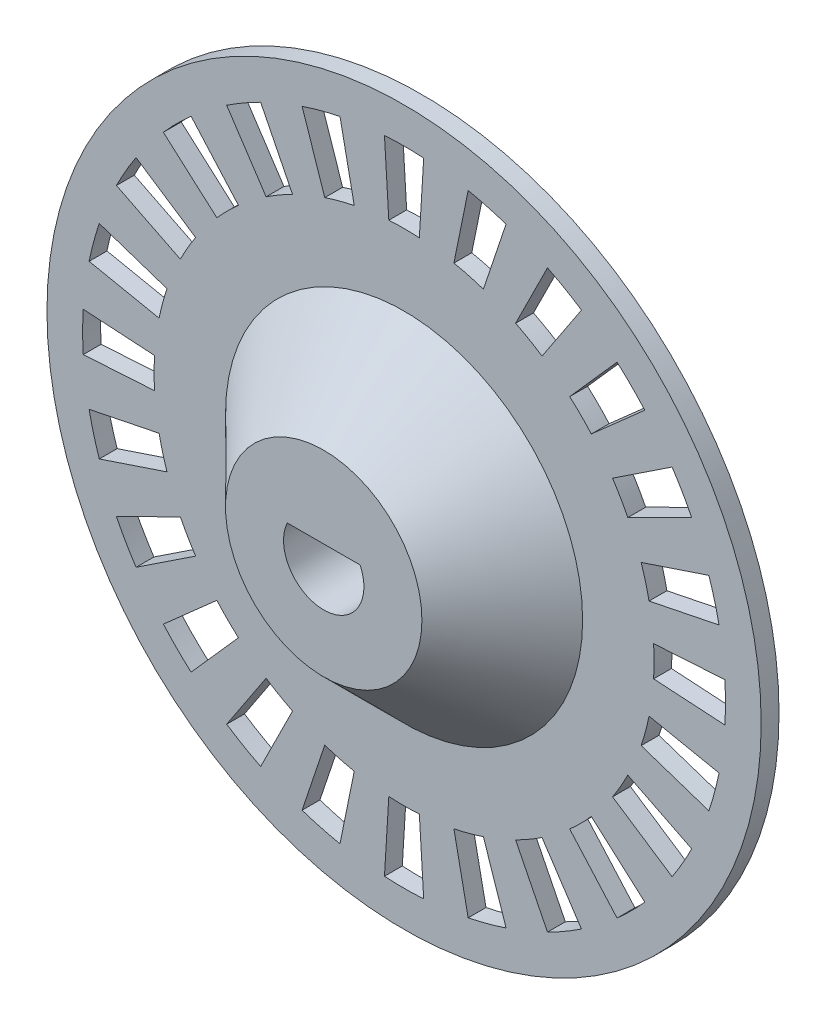
SolidWorks part; units mm, degrees
ref_plane "Alzado" through (0, 0, 0) normal (0, 0, 1) x (1, 0, 0)
ref_plane "Planta" through (0, 0, 0) normal (0, 1, 0) x (1, 0, 0)
ref_plane "Vista lateral" through (0, 0, 0) normal (1, 0, 0) x (0, 0, -1)
sketch "Croquis2" plane through (0, 0, 0) normal (0, 0, 1) x (1, 0, 0)
  line L0 (-2.0396, 0.95) -> (2.0396, 0.95)
  line L1 (-2.5594, -2.25) -> (2.5594, -2.25) construction
  line L2 (0, 18) -> (0, -18) construction
  line L3 (18, 0) -> (-18, 0) construction
  line L4 (-1.0989, 17.9664) -> (-0.8547, 13.9739)
  line L5 (0.8547, 13.9739) -> (1.0989, 17.9664)
  line L6 (3.5886, 17.6386) -> (2.7912, 13.7189)
  line L7 (4.4423, 13.2765) -> (5.7115, 17.0698)
  line L8 (8.0316, 16.1088) -> (6.2468, 12.5291)
  line L9 (7.7271, 11.6744) -> (9.9349, 15.0099)
  line L10 (11.9272, 13.4812) -> (9.2767, 10.4854)
  line L11 (10.4854, 9.2767) -> (13.4812, 11.9272)
  line L12 (15.0099, 9.9349) -> (11.6744, 7.7271)
  line L13 (12.5291, 6.2468) -> (16.1088, 8.0316)
  line L14 (17.0698, 5.7115) -> (13.2765, 4.4423)
  line L15 (13.7189, 2.7912) -> (17.6386, 3.5886)
  line L16 (17.9664, 1.0989) -> (13.9739, 0.8547)
  line L17 (13.9739, -0.8547) -> (17.9664, -1.0989)
  line L18 (17.6386, -3.5886) -> (13.7189, -2.7912)
  line L19 (13.2765, -4.4423) -> (17.0698, -5.7115)
  line L20 (16.1088, -8.0316) -> (12.5291, -6.2468)
  line L21 (11.6744, -7.7271) -> (15.0099, -9.9349)
  line L22 (13.4812, -11.9272) -> (10.4854, -9.2767)
  line L23 (9.2767, -10.4854) -> (11.9272, -13.4812)
  line L24 (9.9349, -15.0099) -> (7.7271, -11.6744)
  line L25 (6.2468, -12.5291) -> (8.0316, -16.1088)
  line L26 (5.7115, -17.0698) -> (4.4423, -13.2765)
  line L27 (2.7912, -13.7189) -> (3.5886, -17.6386)
  line L28 (1.0989, -17.9664) -> (0.8547, -13.9739)
  line L29 (-0.8547, -13.9739) -> (-1.0989, -17.9664)
  line L30 (-3.5886, -17.6386) -> (-2.7912, -13.7189)
  line L31 (-4.4423, -13.2765) -> (-5.7115, -17.0698)
  line L32 (-8.0316, -16.1088) -> (-6.2468, -12.5291)
  line L33 (-7.7271, -11.6744) -> (-9.9349, -15.0099)
  line L34 (-11.9272, -13.4812) -> (-9.2767, -10.4854)
  line L35 (-10.4854, -9.2767) -> (-13.4812, -11.9272)
  line L36 (-15.0099, -9.9349) -> (-11.6744, -7.7271)
  line L37 (-12.5291, -6.2468) -> (-16.1088, -8.0316)
  line L38 (-17.0698, -5.7115) -> (-13.2765, -4.4423)
  line L39 (-13.7189, -2.7912) -> (-17.6386, -3.5886)
  line L40 (-17.9664, -1.0989) -> (-13.9739, -0.8547)
  line L41 (-13.9739, 0.8547) -> (-17.9664, 1.0989)
  line L42 (-17.6386, 3.5886) -> (-13.7189, 2.7912)
  line L43 (-13.2765, 4.4423) -> (-17.0698, 5.7115)
  line L44 (-16.1088, 8.0316) -> (-12.5291, 6.2468)
  line L45 (-11.6744, 7.7271) -> (-15.0099, 9.9349)
  line L46 (-13.4812, 11.9272) -> (-10.4854, 9.2767)
  line L47 (-9.2767, 10.4854) -> (-11.9272, 13.4812)
  line L48 (-9.9349, 15.0099) -> (-7.7271, 11.6744)
  line L49 (-6.2468, 12.5291) -> (-8.0316, 16.1088)
  line L50 (-5.7115, 17.0698) -> (-4.4423, 13.2765)
  line L51 (-2.7912, 13.7189) -> (-3.5886, 17.6386)
  circle A0 centre (0, 0) radius 14
  circle A1 centre (0, 0) radius 2.25
  circle A2 centre (0, 0) radius 18
  circle A3 centre (0, 0) radius 20
  circle A4 centre (0, 0) radius 5
  point P10 (0, -2.25)
  point P113 (0, 0)
  dimension "D1" = 4.5
  dimension "D2" = 40
  dimension "D3" = 4
  dimension "D7" = 2
  dimension "D4" = 3.2
  dimension "D5" = 7
  dimension "D6" = 24
extrude "Saliente-Extruir2" add sketch "Croquis2" along normal blind 1 contours L4 A2 L51 A0 | L6 A2 L5 A0 | L8 A2 L7 A0 | L10 A2 L9 A0 | L12 A2 L11 A0 | L14 A2 L13 A0 | L16 A2 L15 A0 | L18 A2 L17 A0 | L20 A2 L19 A0 | L22 A2 L21 A0 | L24 A2 L23 A0 | L26 A2 L25 A0 | L28 A2 L27 A0 | L30 A2 L29 A0 | L32 A2 L31 A0 | L34 A2 L33 A0 | L36 A2 L35 A0 | L38 A2 L37 A0 | L40 A2 L39 A0 | L42 A2 L41 A0 | L44 A2 L43 A0 | L46 A2 L45 A0 | L48 A2 L47 A0 | L50 A2 L49 A0 | A3 A2 | A4 A1 | A0 A4 | L0 A1 region at (0, 1.4855, 0) region at (-2.0976, 15.9328, 0) region at (0, 13.604, 0) region at (2.0976, 15.9328, 0) region at (-6.1498, 14.847, 0) region at (6.1498, 14.847, 0) region at (-9.783, 12.7494, 0) region at (9.783, 12.7494, 0) region at (-12.7494, 9.783, 0) region at (12.7494, 9.783, 0) region at (-14.847, 6.1498, 0) region at (14.847, 6.1498, 0) region at (-15.9328, 2.0976, 0) region at (15.9328, 2.0976, 0) region at (-15.9328, -2.0976, 0) region at (15.9328, -2.0976, 0) region at (-14.847, -6.1498, 0) region at (14.847, -6.1498, 0) region at (-12.7494, -9.783, 0) region at (12.7494, -9.783, 0) region at (-9.783, -12.7494, 0) region at (9.783, -12.7494, 0) region at (-6.1498, -14.847, 0) region at (6.1498, -14.847, 0) region at (-2.0976, -15.9328, 0) region at (2.0976, -15.9328, 0) region at (-19.4343, 0, 0) region at (-4.8586, 0, 0)
extrude "Saliente-Extruir3" add sketch "Croquis2<5>" along normal blind 5.5 contours A4
sketch "Croquis2<5>" plane through (0, 0, 0) normal (0, 0, 1) x (1, 0, 0) same geometry as "Croquis2"
chamfer "Chaflán1" distance 5 angle 45 1 edges at (5, 0, 1)
extrude "Cortar-Extruir1" cut sketch "Croquis2<6>" along normal through all contours L0 A1 region at (0, -0.4676, 0)
sketch "Croquis2<6>" plane through (0, 0, 0) normal (0, 0, 1) x (1, 0, 0) same geometry as "Croquis2"
